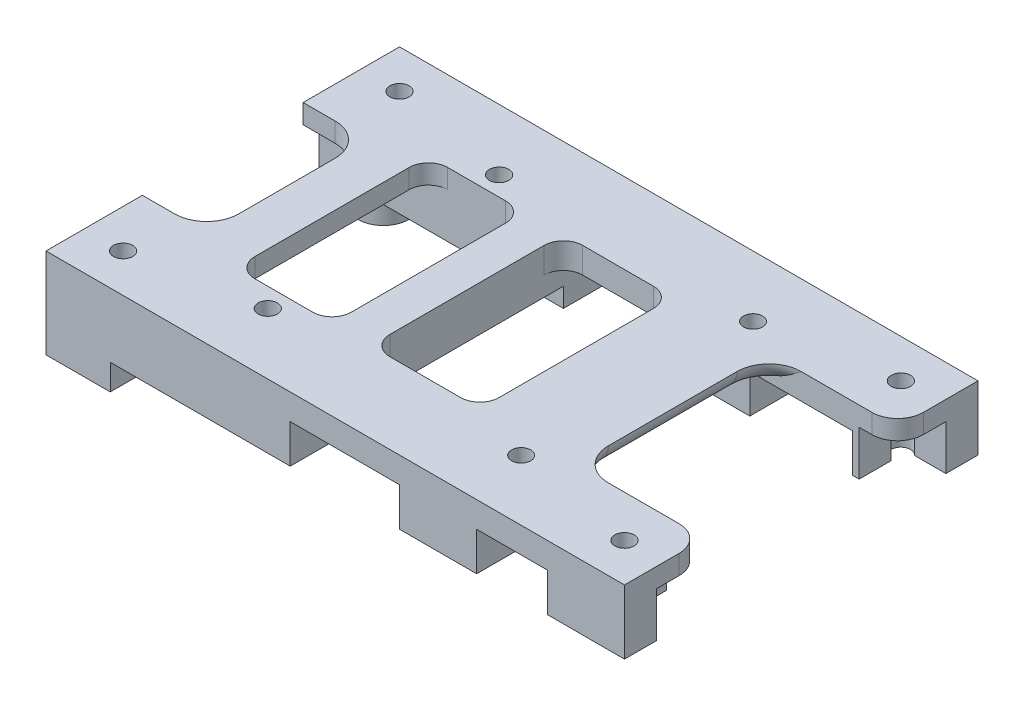
SolidWorks part; units mm, degrees
ref_plane "前视基准面" through (0, 0, 0) normal (0, 0, 1) x (1, 0, 0)
ref_plane "上视基准面" through (0, 0, 0) normal (0, 1, 0) x (1, 0, 0)
ref_plane "右视基准面" through (0, 0, 0) normal (1, 0, 0) x (0, 0, -1)
sketch "草图1" plane through (0, 0, 0) normal (0, 1, 0) x (1, 0, 0)
  line L1 (-45, 27.5) -> (45, 27.5)
  line L2 (-45, 27.5) -> (-45, -27.5)
  line L3 (-45, -27.5) -> (45, -27.5)
  line L4 (45, 27.5) -> (45, -27.5)
  line L5 (-45, 27.5) -> (45, -27.5) construction
  line L6 (-45, -27.5) -> (45, 27.5) construction
  point P0 (0, 0)
  dimension "D1" = 90
  dimension "D2" = 55
extrude "凸台-拉伸1" add sketch "草图1" along normal blind 10
sketch "草图2" plane through (0, 10, 0) normal (0, 1, 0) x (1, 0, 0)
  line L0 (-45, 0) -> (45, 0) construction
  line L1 (-45, 27.5) -> (-45, -27.5) construction
  line L2 (45, -27.5) -> (45, 27.5) construction
  line L3 (-20, 27.5) -> (-20, -27.5) construction
  line L4 (45, 27.5) -> (-45, 27.5) construction
  line L5 (-45, -27.5) -> (45, -27.5) construction
  circle A0 centre (-20, 18) radius 1.5
  circle A1 centre (-20, -18) radius 1.5
  circle A2 centre (19.5, -18.0759) radius 1.48 construction
  circle A3 centre (19.5, 18) radius 1.48 construction
  circle A4 centre (19.5, -18.0759) radius 1.48
  circle A5 centre (19.5, 18) radius 1.48
  dimension "D1" = 3
  dimension "D2" = 18
  dimension "D3" = 25
extrude "切除-拉伸1" cut sketch "草图2" against normal blind 30
sketch "草图3" plane through (0, 0, 0) normal (0, -1, 0) x (1, 0, 0)
  line L0 (-45, -15) -> (35, -15)
  line L6 (45, 0) -> (-45, 0) construction
  line L8 (-45, -27.5) -> (-45, 27.5) construction
  line L11 (-45, 27.5) -> (45, 27.5) construction
  line L12 (-45, 15) -> (35, 15)
  line L13 (-45, 15) -> (-45, -15)
  line L14 (-45, 0) -> (35, 0)
  line L15 (35, 15) -> (35, -15)
  line L17 (45, 27.5) -> (45, -27.5) construction
  line L18 (45, 22.5) -> (39, 22.5)
  line L19 (45, 22.5) -> (45, -22.5)
  line L20 (45, -22.5) -> (39, -22.5)
  line L21 (39, 22.5) -> (39, -22.5)
  line L22 (45, -27.5) -> (-45, -27.5) construction
  dimension "D1" = 6
  dimension "D2" = 5
  dimension "D3" = 12.5
  dimension "D4" = 5
  dimension "D5" = 80
extrude "切除-拉伸2" cut sketch "草图3" against normal blind 7
sketch "草图4" plane through (0, 10, 0) normal (0, 1, 0) x (1, 0, 0)
  line L0 (-45, 0) -> (45, 0) construction
  line L1 (-45, 27.5) -> (-45, -27.5) construction
  line L2 (45, -27.5) -> (45, 27.5) construction
  line L3 (-45, 21.5) -> (45, 21.5) construction
  line L4 (-39, 27.5) -> (-39, -27.5) construction
  line L5 (45, 27.5) -> (-45, 27.5) construction
  line L6 (-45, -27.5) -> (45, -27.5) construction
  line L7 (39, 27.5) -> (39, -27.5) construction
  circle A0 centre (39, 21.5) radius 1.5
  circle A2 centre (-39, 21.5) radius 1.5
  circle A3 centre (-39, -21.5) radius 1.5
  circle A4 centre (39, -21.5) radius 1.5
  dimension "D3" = 3
  dimension "D4" = 3
  dimension "D1" = 78
  dimension "D2" = 21.5
  dimension "D5" = 6
extrude "切除-拉伸3" cut sketch "草图4" against normal blind 20
sketch "草图8" plane through (0, 10, 0) normal (0, 1, 0) x (1, 0, 0)
  line L0 (-45, 27.5) -> (-45, -27.5) construction
  line L1 (-45, 12.5) -> (-35, 12.5)
  line L2 (-45, 12.5) -> (-45, -12.5)
  line L3 (-45, -12.5) -> (-35, -12.5)
  line L4 (-35, 12.5) -> (-35, -12.5)
  line L5 (45, -27.5) -> (45, 27.5) construction
  line L6 (45, 15) -> (25, 15)
  line L7 (45, 15) -> (45, -15)
  line L8 (45, -15) -> (25, -15)
  line L9 (25, 15) -> (25, -15)
  line L10 (45, 27.5) -> (-45, 27.5) construction
  line L11 (-45, -27.5) -> (45, -27.5) construction
  dimension "D1" = 15
  dimension "D2" = 15
  dimension "D3" = 10
  dimension "D4" = 12.5
  dimension "D5" = 12.5
  dimension "D6" = 20
extrude "切除-拉伸6" cut sketch "草图8" against normal blind 20
sketch "草图10" plane through (0, 0, 0) normal (0, -1, 0) x (1, 0, 0)
  line L0 (-45, 27.5) -> (45, 27.5) construction
  line L1 (22, 27.5) -> (33, 27.5)
  line L2 (22, 27.5) -> (22, -27.5)
  line L3 (22, -27.5) -> (33, -27.5)
  line L4 (33, 27.5) -> (33, -27.5)
  line L5 (45, -27.5) -> (-45, -27.5) construction
  line L6 (45, 27.5) -> (45, 22.5) construction
  line L7 (-7, 27.5) -> (10, 27.5)
  line L8 (-7, 27.5) -> (-7, -27.5)
  line L9 (-7, -27.5) -> (10, -27.5)
  line L10 (10, 27.5) -> (10, -27.5)
  dimension "D1" = 11
  dimension "D2" = 12
  dimension "D3" = 12
  dimension "D4" = 17
extrude "切除-拉伸8" cut sketch "草图10" against normal blind 6
fillet "圆角3" radius 5 4 edges at (-35, 8.5, 12.5) (-35, 8.5, -12.5) (25, 8.5, 15) (25, 8.5, -15)
sketch "草图11" plane through (0, 7, 0) normal (0, -1, 0) x (1, 0, 0)
  line L0 (-45, -15) -> (-7, -15) construction
  line L1 (-7, 15) -> (-13, 15)
  line L2 (-7, 15) -> (-7, -15)
  line L3 (-7, -15) -> (-13, -15)
  line L4 (-13, 15) -> (-13, -15)
  line L5 (10, -15) -> (22, -15) construction
  line L6 (10, 15) -> (16, 15)
  line L7 (10, 15) -> (10, -15)
  line L8 (10, -15) -> (16, -15)
  line L9 (16, 15) -> (16, -15)
  dimension "D1" = 6
  dimension "D2" = 6
extrude "凸台-拉伸3" add sketch "草图11" along normal blind 4
chamfer "倒角3" distance 5 angle 45 2 edges at (33, 3, 15) (33, 3, -15)
fillet "圆角7" radius 3 7 edges at (30, 8.5, 15) (25, 7, 0) (25, 8.5, -10) (25, 8.5, 10) (30, 8.5, -15) (26.4645, 7, 13.5355) (26.4645, 7, -13.5355)
sketch "草图12" plane through (0, 7, 0) normal (0, -1, 0) x (1, 0, 0)
  line L0 (-45, -15) -> (-7, -15) construction
  line L1 (-13, 15) -> (-28, 15)
  line L2 (-13, 15) -> (-13, -15)
  line L3 (-13, -15) -> (-28, -15)
  line L4 (-7, -15) -> (10, -15)
  line L5 (10, -15) -> (10, 15)
  line L6 (10, 15) -> (-7, 15)
  line L7 (-7, 15) -> (-7, -15)
  line L8 (-7, -15) -> (10, -15)
  line L9 (10, -15) -> (10, 15)
  line L10 (10, 15) -> (-7, 15)
  line L11 (-7, 15) -> (-7, -15)
  line L12 (-28, 15) -> (-28, -15)
  dimension "D2" = 15
  dimension "D1" = 0
extrude "切除-拉伸9" cut sketch "草图12" against normal blind 6
fillet "圆角8" radius 3 8 edges at (-13, 6.5, -15) (-13, 6.5, 15) (-28, 8.5, 15) (-28, 8.5, -15) (-7, 8, -15) (-7, 8, 15) (10, 8, -15) (10, 8, 15)
fillet "圆角9" radius 4 3 edges at (16, 7, 0) (16, 5, -15) (16, 5, 15)
sketch "草图13" plane through (0, 0, 0) normal (0, -1, 0) x (1, 0, 0)
  line L1 (-35, 27.5) -> (-45, 27.5)
  line L3 (-35, -27.5) -> (-45, -27.5)
  line L4 (-45, 27.5) -> (-45, 15)
  line L6 (-45, -15) -> (-45, -27.5)
  line L7 (-35, 15) -> (-45, 15)
  line L9 (-35, -15) -> (-45, -15)
  line L12 (-35, 27.5) -> (-35, 15)
  line L13 (-35, -15) -> (-35, -27.5)
  dimension "D1" = 10
extrude "凸台-拉伸4" add sketch "草图13" along normal blind 4
fillet "圆角10" radius 4 2 edges at (-35, -2, -15) (-35, -2, 15)
fillet "圆角11" radius 4 2 edges at (45, 8.5, 15) (45, 8.5, -15)
sketch "草图14" plane through (0, 0, -27.5) normal (0, 0, -1) x (-1, 0, 0)
  line L0 (-45, 10) -> (-45, 0) construction
  line L1 (-45, 10) -> (45, 10) construction
  circle A0 centre (-28, 8) radius 1
  circle A1 centre (7, 8) radius 1
  dimension "D1" = 2
  dimension "D2" = 2
  dimension "D3" = 35
  dimension "D4" = 17
  dimension "D5" = 2
  dimension "D6" = 2
extrude "切除-拉伸10" cut sketch "草图14" against normal blind 10
